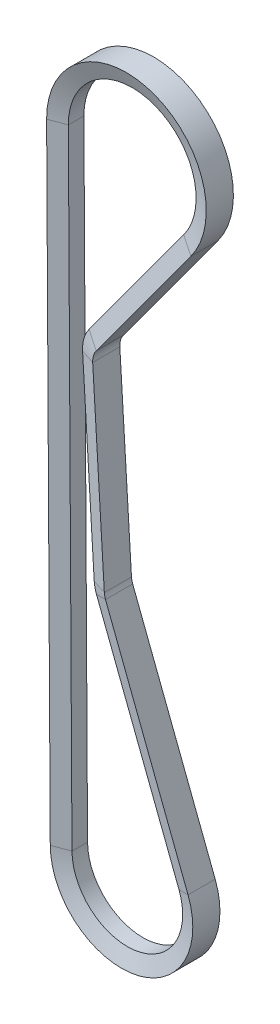
SolidWorks part; units mm, degrees
ref_plane "Front Plane" through (0, 0, 0) normal (0, 0, 1) x (1, 0, 0)
ref_plane "Top Plane" through (0, 0, 0) normal (0, 1, 0) x (1, 0, 0)
ref_plane "Right Plane" through (0, 0, 0) normal (1, 0, 0) x (0, 0, -1)
sketch "Sketch2" plane through (0, 0, 0) normal (0, 0, 1) x (1, 0, 0)
  line L0 (0, 0) -> (1, 0) construction
  line L1 (0, 0) -> (0, 1) construction
  line L9 (24.3053, 203.443) -> (-8.9026, 158.1263)
  line L10 (-10.1191, 153.9914) -> (-6.0341, 86.1142)
  line L11 (-5.6219, 84.215) -> (23.3319, 8.979)
  line L12 (-24.9996, -0.1454) -> (-26.2794, 219.8304)
  arc A4 (-26.2794, 219.8304) -> (24.3053, 203.443) centre (1.7202, 219.9933) cw
  arc A5 (-8.9026, 158.1263) -> (-10.1191, 153.9914) centre (-3.7806, 154.3729) ccw
  arc A6 (-6.0341, 86.1142) -> (-5.6219, 84.215) centre (0.3044, 86.4957) ccw
  arc A7 (23.3319, 8.979) -> (-24.9996, -0.1454) centre (0, 0) cw
ref_plane "Plane4" through (23.3319, 8.979, 0) normal (0.3592, -0.9333, 0) x (0, 0, -1)
sketch "Sketch3" plane through (23.3319, 8.979, 0) normal (0.3592, -0.9333, 0) x (0, 0, -1)
  line L0 (-4.7625, 0) -> (4.7625, 0)
  line L1 (-4.7625, 0) -> (-2.7286, -5.588)
  line L2 (-2.7286, -5.588) -> (2.7286, -5.588)
  line L3 (2.7286, -5.588) -> (4.7625, 0)
  line L4 (0, 0) -> (0, -5.588) construction
  point P4 (-3.5872, -5.588)
  point P8 (0, 0)
  point P10 (-2.7243, 5.588)
  point P11 (-6.4464, -5.588)
  dimension "D1" = 9.525
  dimension "D2" = 5.588
  dimension "D3" = 40
sweep "Sweep1" add profiles "Sketch3" path "Sketch2"
